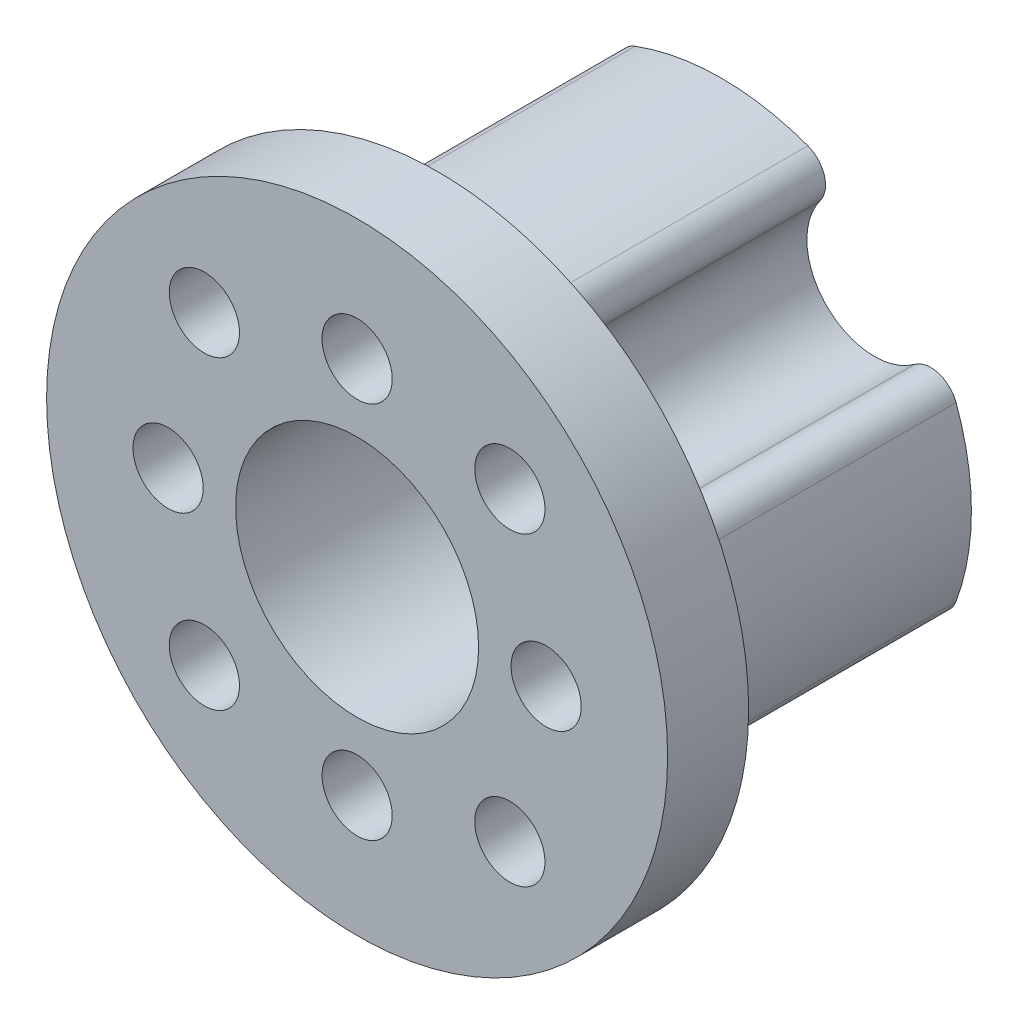
SolidWorks part; units mm, degrees
ref_plane "Plan de face" through (0, 0, 0) normal (0, 0, 1) x (1, 0, 0)
ref_plane "Plan de dessus" through (0, 0, 0) normal (0, 1, 0) x (1, 0, 0)
ref_plane "Plan de droite" through (0, 0, 0) normal (1, 0, 0) x (0, 0, -1)
sketch "Esquisse1" plane through (0, 0, 0) normal (0, 0, 1) x (1, 0, 0)
  circle A0 centre (0, 0) radius 9.25
  dimension "D1" = 18.5
extrude "Boss.-Extru.1" add sketch "Esquisse1" along normal blind 13.5
sketch "Esquisse2" plane through (0, 0, 13.5) normal (0, 0, 1) x (1, 0, 0)
  line L0 (0, 0) -> (7, 0) construction
  circle A0 centre (7, 0) radius 1.3
  circle A1 centre (0, -7) radius 1.3
  circle A2 centre (-7, 0) radius 1.3
  circle A3 centre (0, 7) radius 1.3
  point P13 (0, 0)
  dimension "D1" = 2.6
  dimension "D2" = 7
  dimension "D3" = 4
extrude "Enlèv. mat.-Extru.1" cut sketch "Esquisse2" against normal through all both and the other way through all
sketch "Esquisse3" plane through (0, 0, 13.5) normal (0, 0, 1) x (1, 0, 0)
  circle A1 centre (0, 0) radius 4.5
  dimension "D1" = 9
extrude "Enlèv. mat.-Extru.2" cut sketch "Esquisse3" against normal through all both and the other way through all
sketch "Esquisse4" plane through (0, 0, 13.5) normal (0, 0, 1) x (1, 0, 0)
  circle A0 centre (0, 0) radius 9.25
  circle A1 centre (0, 0) radius 11.5
  circle A2 centre (0, 0) radius 9.25 construction
  dimension "D1" = 23
extrude "Boss.-Extru.2" add sketch "Esquisse4" against normal blind 3
sketch "Esquisse5" plane through (0, 0, 13.5) normal (0, 0, 1) x (1, 0, 0)
  line L0 (5.6569, 5.6569) -> (0, 0) construction
  line L1 (0, 0) -> (2.5725, 0) construction
  circle A0 centre (5.6569, 5.6569) radius 2.5
  circle A1 centre (5.6569, -5.6569) radius 2.5
  circle A2 centre (-5.6569, -5.6569) radius 2.5
  circle A3 centre (-5.6569, 5.6569) radius 2.5
  point P13 (0, 0)
  point P14 (0, 0)
  dimension "D3" = 5
  dimension "D1" = 45
  dimension "D2" = 8
  dimension "D4" = 4
extrude "Enlèv. mat.-Extru.3" cut sketch "Esquisse5" against normal through all both and the other way through all
sketch "Esquisse6" plane through (0, 0, 13.5) normal (0, 0, 1) x (1, 0, 0)
  circle A0 centre (-5.6569, 5.6569) radius 2.5
  circle A1 centre (-5.6569, 5.6569) radius 1.3
  circle A2 centre (-5.6569, 5.6569) radius 2.5 construction
  circle A3 centre (5.6569, 5.6569) radius 2.5
  circle A4 centre (5.6569, 5.6569) radius 1.3
  circle A5 centre (5.6569, -5.6569) radius 2.5
  circle A6 centre (5.6569, -5.6569) radius 1.3
  circle A7 centre (-5.6569, -5.6569) radius 2.5
  circle A8 centre (-5.6569, -5.6569) radius 1.3
  point P18 (0, 0)
  dimension "D1" = 2.6
  dimension "D2" = 4
extrude "Boss.-Extru.3" add sketch "Esquisse6" against normal up to vertex (3 mm away) up to point (-7.9667, 4.7005, 10.5)
fillet "Congé1" radius 1 8 edges at (7.9667, -4.7005, 5.25) (4.7005, -7.9667, 5.25) (-4.7005, -7.9667, 5.25) (-7.9667, -4.7005, 5.25) (-7.9667, 4.7005, 5.25) (-4.7005, 7.9667, 5.25) (4.7005, 7.9667, 5.25) (7.9667, 4.7005, 5.25)
